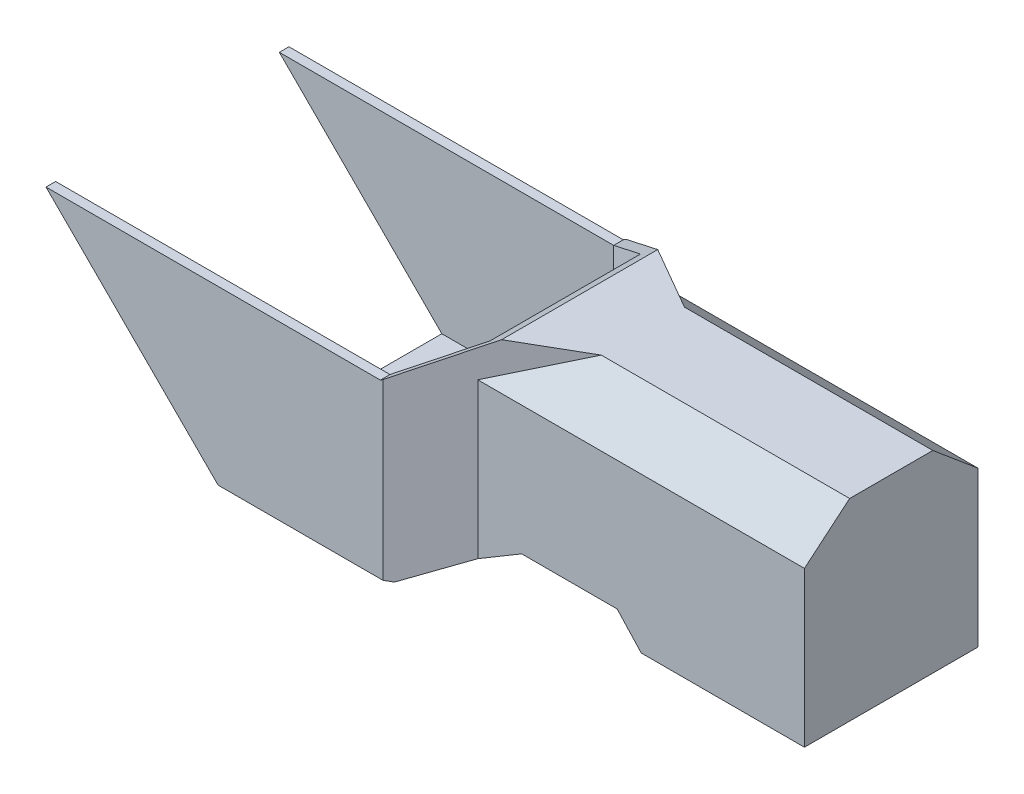
SolidWorks part; units mm, degrees
ref_plane "前视基准面" through (0, 0, 0) normal (0, 0, 1) x (1, 0, 0)
ref_plane "上视基准面" through (0, 0, 0) normal (0, 1, 0) x (1, 0, 0)
ref_plane "右视基准面" through (0, 0, 0) normal (1, 0, 0) x (0, 0, -1)
sketch "草图1" plane through (0, 0, 0) normal (0, 0, 1) x (1, 0, 0)
  line L0 (-25, 825.8203) -> (-25, 545.8203) construction
  line L1 (-25, 545.8203) -> (321.4823, 199.338) construction
  line L2 (321.4823, 199.338) -> (1236.4823, 199.338) construction
  line L3 (0, 0) -> (2679.8184, 0) construction
  line L4 (2679.8184, 350) -> (-1550.6743, 350) construction
  line L5 (-1550.6743, 350) -> (-1550.6743, 0) construction
  line L6 (-1550.6743, 0) -> (0, 0) construction
  line L7 (-1550.6743, 300) -> (2679.8184, 300) construction
  line L8 (-1550.6743, 70) -> (2679.8184, 70) construction
  line L9 (-252.3327, 1200) -> (-252.3327, 70) construction
  line L10 (1249.6005, 496.6011) -> (1549.6005, 496.6011) construction
  line L11 (1249.6005, 496.6011) -> (1249.6005, 196.6011) construction
  line L12 (1249.6005, 196.6011) -> (1549.6005, 196.6011) construction
  line L13 (1549.6005, 496.6011) -> (1549.6005, 196.6011) construction
  line L14 (770.4866, 746.7717) -> (770.4866, 70) construction
  line L15 (-252.3327, 1200) -> (770.4866, 746.7717) construction
  line L16 (35.7687, 962.9596) -> (473.3974, 769.039) construction
  line L17 (-252.3327, 597.3138) -> (234.2786, 70) construction
  line L18 (1599.1649, 70) -> (1599.1649, 886.5201) construction
  line L19 (770.4866, 597.3138) -> (507.7866, 597.3138) construction
  circle A0 centre (-25, 825.8203) radius 150 construction
  circle A1 centre (-25, 545.8203) radius 100 construction
  circle A2 centre (321.4823, 199.338) radius 100 construction
  point P31 (1599.1649, 496.6011)
  point P32 (1599.1649, 196.6011)
  point P33 (0, 0)
  point P34 (0, 0)
  point P40 (22.0319, 300)
  dimension "D1" = 300
  dimension "D2" = 200
  dimension "D3" = 200
  dimension "D4" = 490
  dimension "D5" = 280
  dimension "D6" = 915
  dimension "D7" = 350
  dimension "D8" = 300
  dimension "D9" = 45
  dimension "D10" = 50
  dimension "D11" = 70
  dimension "D12" = 300
  dimension "D13" = 300
  dimension "D15" = 1200
  dimension "D16" = 100
  dimension "D17" = 262.7
ref_plane "Plane1" through (1599.1649, 0, 0) normal (1, 0, 0) x (0, 0, -1)
sketch "Sketch1" plane through (1599.1649, 0, 0) normal (1, 0, 0) x (0, 0, -1)
  line L1 (0, 176.6011) -> (-200, 176.6011)
  line L2 (0, 176.6011) -> (0, 626.6011)
  line L3 (0, 626.6011) -> (-200, 626.6011)
  line L4 (-200, 176.6011) -> (-200, 626.6011)
  dimension "D1" = 200
  dimension "D2" = 450
extrude "Boss-Extrude1" add sketch "Sketch1" against normal up to vertex (828.6783 mm away) up to point (770.4866, 597.3138, 0)
sketch "Sketch2" plane through (770.4866, 0, 0) normal (-1, 0, 0) x (0, 0, 1)
  line L1 (0, 626.6011) -> (290, 626.6011)
  line L2 (0, 626.6011) -> (0, 95)
  line L3 (0, 95) -> (290, 95)
  line L4 (290, 626.6011) -> (290, 95)
  dimension "D1" = 290
  dimension "D2" = 25
extrude "Boss-Extrude2" add sketch "Sketch2" along normal up to vertex (1022.8193 mm away) up to point (-252.3327, 597.3138, 0)
sketch "Sketch6" plane through (0, 0, 0) normal (0, 0, 1) x (1, 0, 0)
  line L0 (884.1883, 244.27) -> (633.3752, 95)
  line L1 (-252.3327, 95) -> (770.4866, 95) construction
  line L2 (633.3752, 95) -> (1003.992, 95)
  line L6 (884.1883, 244.27) -> (1149.5971, 244.27)
  line L7 (1149.5971, 244.27) -> (1287.1687, 95)
  line L8 (1287.1687, 95) -> (1003.992, 95)
  point P5 (931.3609, 236.77)
  point P8 (884.1883, 244.27)
  dimension "D1" = 50
extrude "Cut-Extrude6" cut sketch "Sketch6" along normal through all
chamfer "Chamfer3" [suppressed] distance 25 angle 70
sketch "Sketch7" plane through (0, 626.6011, 0) normal (0, 1, 0) x (1, 0, 0)
  line L0 (770.4866, -200) -> (614.602, -290)
  line L1 (-252.3327, -290) -> (770.4866, -290) construction
  line L2 (614.602, -290) -> (770.4866, -290)
  line L3 (770.4866, -290) -> (770.4866, -200)
  dimension "D1" = 60
sketch3d "3DSketch4" [suppressed]
  line L0 (770.4866, 176.6011, 175) -> (770.4866, 245.288, 200) construction
  line L1 (770.4866, 626.6011, 200) -> (770.4866, 245.288, 200) construction
  line L2 (770.4866, 176.6011, 175) -> (770.4866, 245.288, 200)
  line L3 (770.4866, 626.6011, 200) -> (770.4866, 245.288, 200)
extrude "Cut-Extrude7" cut sketch "Sketch7" against normal through all
chamfer "Chamfer4" distance 85 angle 50 1 edges at (1184.8258, 626.6011, 200) first distance on face at (1140.7216, 324.5065, 200)
sketch "Sketch3" plane through (0, 0, 0) normal (0, 0, 1) x (1, 0, 0)
  line L0 (-284.7595, 548.7202) -> (216.2601, 47.7007)
  line L1 (216.2601, 47.7007) -> (-284.7595, 47.7007)
  line L2 (-284.7595, 47.7007) -> (-284.7595, 548.7202)
extrude "Cut-Extrude1" cut sketch "Sketch3" along normal through all
sketch "Sketch4" plane through (0, 0, 0) normal (0, 0, 1) x (1, 0, 0)
  line L0 (823.1133, 656.0766) -> (614.602, 516.2934)
  line L1 (614.602, 516.2934) -> (-377.1346, 516.2934)
  line L2 (-377.1346, 516.2934) -> (-377.1346, 689.221)
  line L3 (-377.1346, 689.221) -> (823.1133, 656.0766)
  point P2 (0, 0)
  point P7 (823.1133, 661.6154)
extrude "Cut-Extrude4" cut sketch "Sketch4" against normal through all and the other way through all
mirror "Mirror1" about plane through (0, 0, 0) normal (0, 0, 1) of bodies 104
shell "Shell1" thickness 25 removed face at (-41.686, 305.6467, 0) removed face at (696.8737, 571.4473, 0) removed face at (181.1347, 516.2934, 0) outward yes
